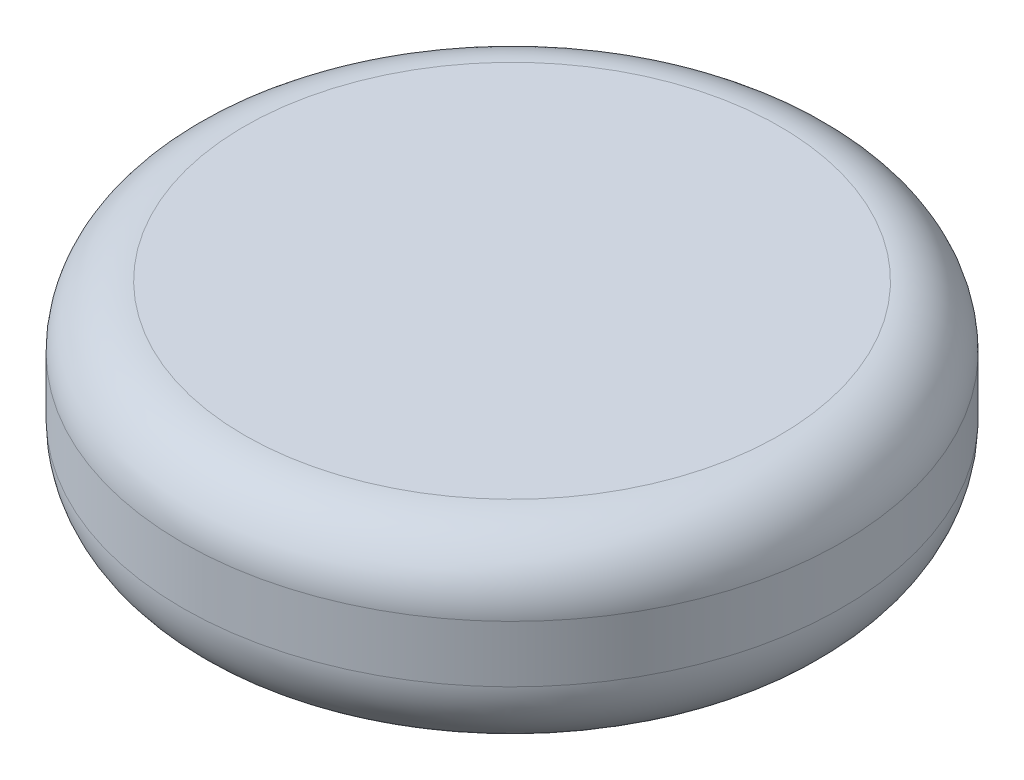
SolidWorks part; units mm, degrees
ref_plane "前视基准面" through (0, 0, 0) normal (0, 0, 1) x (1, 0, 0)
ref_plane "上视基准面" through (0, 0, 0) normal (0, 1, 0) x (1, 0, 0)
ref_plane "右视基准面" through (0, 0, 0) normal (1, 0, 0) x (0, 0, -1)
sketch "草图4" plane through (0, 0, 0) normal (0, 1, 0) x (1, 0, 0)
  circle A0 centre (0, 0) radius 250
extrude "凸台-拉伸2" add sketch "草图4" along normal blind 150
fillet "圆角1" radius 60 1 edges at (0, 0, 250)
fillet "圆角2" radius 47 1 edges at (0, 150, 250)
sketch "草图16" plane through (0, 0, 0) normal (0, 1, 0) x (1, 0, 0)
  circle A0 centre (0, 0) radius 190
extrude "切除-拉伸1" cut sketch "草图16" along normal blind 25
fillet "圆角3" radius 25 1 edges at (0, 0, 190)
chamfer "倒角1" distance 10 angle 45 1 edges at (0, 25, 190) first distance on face at (0, 25, 190)
